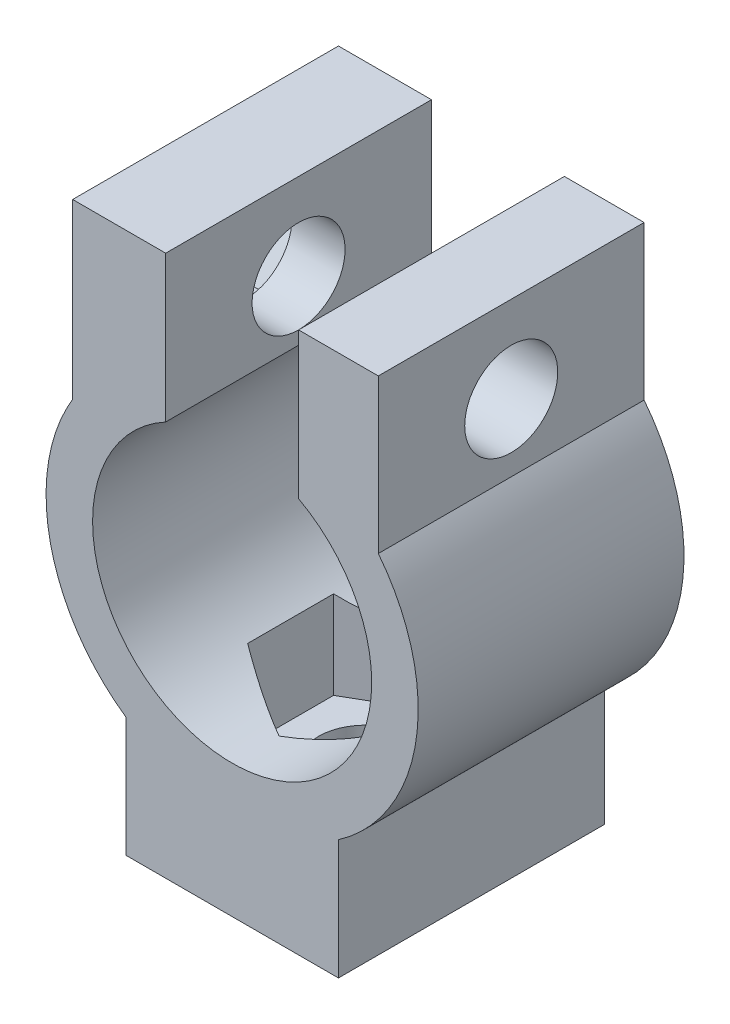
SolidWorks part; units mm, degrees
ref_plane "Plano frontal" through (0, 0, 0) normal (0, 0, 1) x (1, 0, 0)
ref_plane "Plano superior" through (0, 0, 0) normal (0, 1, 0) x (1, 0, 0)
ref_plane "Plano direito" through (0, 0, 0) normal (1, 0, 0) x (0, 0, -1)
sketch "Esboço1" plane through (0, 0, 0) normal (0, 0, 1) x (1, 0, 0)
  line L0 (-4, 0) -> (4, 0)
  line L1 (4, 0) -> (4, 4.5054)
  line L2 (0, 0) -> (0, 17.2113) construction
  line L3 (2.5, 14.8665) -> (2.5, 20.3665)
  line L4 (2.5, 20.3665) -> (5.5, 20.3665)
  line L5 (5.5, 20.3665) -> (5.5, 14.5801)
  line L6 (-5.5, 20.3665) -> (-5.5, 14.5801)
  line L7 (-2.5, 20.3665) -> (-5.5, 20.3665)
  line L8 (-2.5, 14.8665) -> (-2.5, 20.3665)
  line L9 (-4, 0) -> (-4, 4.5054)
  arc A0 (4, 4.5054) -> (5.5, 14.5801) centre (0, 10.25) ccw
  arc A1 (-2.5, 14.8665) -> (2.5, 14.8665) centre (0, 10.25) ccw
  arc A2 (-4, 4.5054) -> (-5.5, 14.5801) centre (0, 10.25) cw
  point P5 (5.391, 13.3062)
  point P7 (5, 16.8896)
  point P18 (2.5, 14.4207)
  point P19 (0, 5)
  dimension "D1" = 1.75
  dimension "D2" = 10.5
  dimension "D3" = 3
  dimension "D4" = 5.5
  dimension "D5" = 5
  dimension "D6" = 5
  dimension "D7" = 8
extrude "Ressalto-extrusão1" add sketch "Esboço1" along normal mid plane 10
sketch "Esboço3" plane through (0, 20.3665, 0) normal (0, 1, 0) x (1, 0, 0)
  line L1 (0, 3.2332) -> (-2.8, 1.6166)
  line L2 (-2.8, 1.6166) -> (-2.8, -1.6166)
  line L3 (-2.8, -1.6166) -> (0, -3.2332)
  line L4 (0, -3.2332) -> (2.8, -1.6166)
  line L5 (2.8, -1.6166) -> (2.8, 1.6166)
  line L6 (2.8, 1.6166) -> (0, 3.2332)
  circle A0 centre (0, 0) radius 2.8 construction
  dimension "D1" = 5.6
extrude "Corte-extrusão1" cut sketch "Esboço3" against normal offset from surface (7.8665 mm away) 2.5 from offset 10 up to face at (0, 0, 0) offset against normal yes
sketch "Esboço4" plane through (0, 20.3665, 0) normal (0, 1, 0) x (1, 0, 0)
  circle A0 centre (0, 0) radius 1.75
  dimension "D1" = 3.5
extrude "Corte-extrusão2" cut sketch "Esboço4" against normal through all
sketch "Esboço5" plane through (5.5, 0, 0) normal (1, 0, 0) x (0, 0, -1)
  line L1 (-5, 20.3665) -> (5, 20.3665) construction
  circle A0 centre (0, 17.1165) radius 1.75
  point P2 (0, 0)
  dimension "D1" = 3.5
  dimension "D2" = 1.5
extrude "Corte-extrusão3" cut sketch "Esboço5" against normal through all both and the other way through all
sketch "Esboço6" plane through (-5.5, 0, 0) normal (-1, 0, 0) x (0, 0, 1)
  line L0 (5, 4.5054) -> (5, 14.5801) construction
  line L1 (-5, 20.3665) -> (5, 20.3665)
  line L2 (-5, 20.3665) -> (-5, 13.1165)
  line L3 (-5, 13.1165) -> (5, 13.1165)
  line L4 (5, 20.3665) -> (5, 13.1165)
  line L6 (3.2332, 17.1165) -> (1.6166, 19.9165)
  line L7 (1.6166, 19.9165) -> (-1.6166, 19.9165)
  line L8 (-1.6166, 19.9165) -> (-3.2332, 17.1165)
  line L9 (-3.2332, 17.1165) -> (-1.6166, 14.3165)
  line L10 (-1.6166, 14.3165) -> (1.6166, 14.3165)
  line L11 (1.6166, 14.3165) -> (3.2332, 17.1165)
  circle A0 centre (0, 17.1165) radius 2.8 construction
  point P8 (5, 12.9527)
  line M4 (-5, 14.5801) -> (5, 14.5801)
  circle M5 centre (0, 17.1165) radius 1.75
  line M6 (-5, 14.5801) -> (5, 14.5801)
  dimension "D1" = 5.6
  dimension "D2" = 1.2
extrude "Ressalto-extrusão2" add sketch "Esboço6" along normal blind 0.5
extrude "Corte-extrusão4" cut sketch "Esboço6<2>" along normal blind 1.5 and the other way blind 1 contours L11 L6 L7 L8 L9 M6 M4 M5 | L10 L11 L9 M6 M4 region at (-5.5, 14.4503, 0) region at (-5.5, 15.8903, -2.4284)
sketch "Esboço6<2>" plane through (-5.5, 0, 0) normal (-1, 0, 0) x (0, 0, 1) same geometry as "Esboço6"
